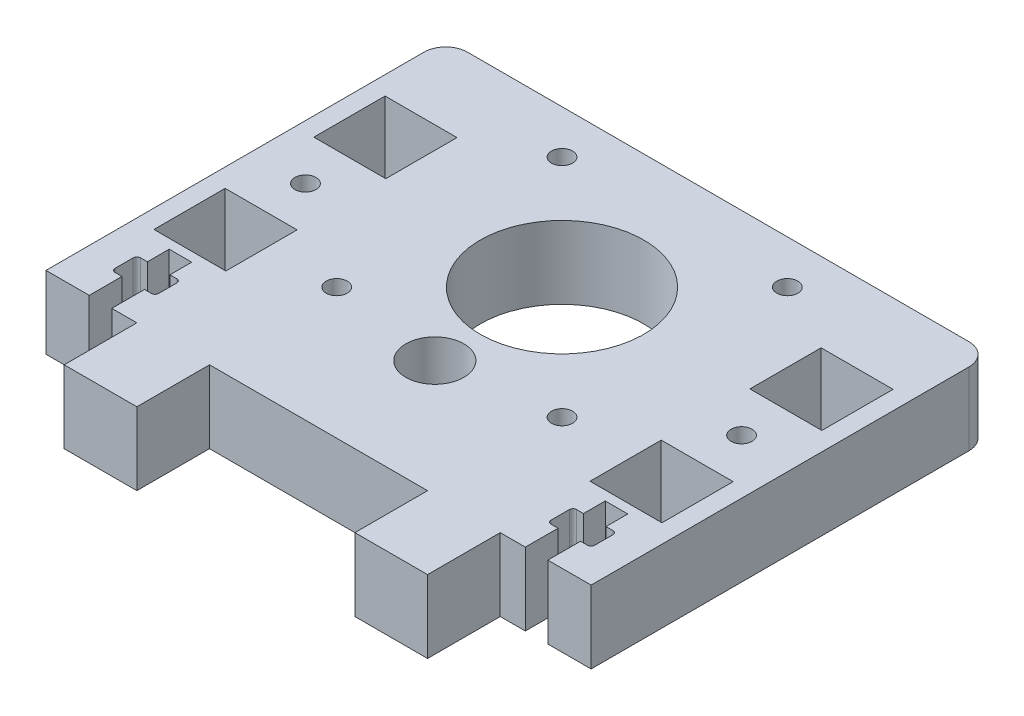
SolidWorks part; units mm, degrees
ref_plane "Front Plane" through (0, 0, 0) normal (0, 0, 1) x (1, 0, 0)
ref_plane "Top Plane" through (0, 0, 0) normal (0, 1, 0) x (1, 0, 0)
ref_plane "Right Plane" through (0, 0, 0) normal (1, 0, 0) x (0, 0, -1)
sketch "Sketch1" plane through (0, 0, 0) normal (0, 1, 0) x (1, 0, 0)
  line L0 (0, 29) -> (0, -6) construction
  line L1 (-34.5, 29) -> (0, 29)
  line L2 (-37.5, 26) -> (-37.5, -26)
  line L3 (-37.5, -26) -> (-25, -26)
  line L4 (0, 29) -> (0, 18.75)
  line L5 (0, -3.75) -> (0, -6)
  line L6 (0, -14) -> (0, -26) construction
  line L7 (-11.25, 7.5) -> (0, 7.5) construction
  line L8 (0, -14) -> (0, -26)
  line L9 (-30, 18.1) -> (-30, 8.3) construction
  line L10 (-37.5, 2.2) -> (0, 2.2) construction
  line L11 (-34.95, 18.1) -> (-25.05, 18.1)
  line L12 (-34.95, 18.1) -> (-34.95, 8.3)
  line L13 (-34.95, 8.3) -> (-25.05, 8.3)
  line L14 (-25.05, 18.1) -> (-25.05, 8.3)
  line L15 (-34.95, 18.1) -> (-25.05, 8.3) construction
  line L16 (-34.95, 8.3) -> (-25.05, 18.1) construction
  line L17 (-34.95, -3.9) -> (-25.05, -13.7) construction
  line L18 (-34.95, -13.7) -> (-25.05, -3.9) construction
  line L19 (-25.05, -13.7) -> (-25.05, -3.9)
  line L20 (-34.95, -3.9) -> (-25.05, -3.9)
  line L21 (-34.95, -13.7) -> (-34.95, -3.9)
  line L22 (-34.95, -13.7) -> (-25.05, -13.7)
  line L23 (-30, -3.9) -> (-30, -13.7) construction
  line L24 (-30, -8.8) -> (-30, 13.2) construction
  line L25 (0, 7.5) -> (-15.5, 23) construction
  line L35 (-15, -26) -> (0, -26)
  line L43 (-20, -36) -> (-20, -24.5) construction
  line L44 (-15, -26) -> (-15, -36)
  line L45 (-15, -36) -> (-25, -36)
  line L46 (-25, -36) -> (-25, -26)
  arc A1 (-34.5, 29) -> (-37.5, 26) centre (-34.5, 26) ccw
  arc A2 (0, 18.75) -> (0, -3.75) centre (0, 7.5) ccw
  circle A4 centre (-15.5, 23) radius 1.45
  circle A6 centre (-15.5, -8) radius 1.45
  circle A7 centre (-30, 2.2) radius 1.45
  arc A10 (0, -6) -> (0, -14) centre (0, -10) ccw
  point P0 (0, 0)
  point P28 (-30, 13.2)
  point P39 (-30, -8.8)
  dimension "D7" = 22.5
  dimension "D17" = 8
  dimension "D14" = 2.9
  dimension "D6" = 3
  dimension "D19" = 2.9
  dimension "D1" = 55
  dimension "D9" = 9.9
  dimension "D10" = 9.8
  dimension "D22" = 10
  dimension "D23" = 10
  dimension "D16" = 17.5
  dimension "D11" = 22
  dimension "D13" = 2.2
  dimension "D3" = 37.5
  dimension "D4" = 31
  dimension "D5" = 15.5
  dimension "D15" = 26
  dimension "D18" = 37.5
  dimension "D20" = 20
  dimension "D8" = 16
  dimension "D12" = 30
extrude "MainLayout" add sketch "Sketch1" along normal blind 10
sketch "Sketch2" plane through (0, 10, 0) normal (0, 1, 0) x (1, 0, 0)
  line L0 (-30, -26) -> (-30, -15) construction
  line L1 (-28.45, -21.5) -> (-28.45, -26)
  line L2 (-37.5, -26) -> (-25, -26) construction
  line L3 (-28.45, -15) -> (-31.55, -15)
  line L4 (-31.55, -15) -> (-31.55, -18)
  line L5 (-31.55, -18) -> (-32.5, -18)
  line L6 (-33, -18.5) -> (-33, -21)
  line L7 (-32.5, -21.5) -> (-31.55, -21.5)
  line L8 (-31.55, -21.5) -> (-31.55, -26)
  line L9 (-31.55, -26) -> (-28.45, -26)
  line L10 (-27.5, -21.5) -> (-28.45, -21.5)
  line L11 (-27, -18.5) -> (-27, -21)
  line L12 (-28.45, -18) -> (-27.5, -18)
  line L13 (-28.45, -15) -> (-28.45, -18)
  line L14 (0, -26) -> (0, -14) construction
  line L30 (-30, -26) -> (-30, -15) construction
  arc A0 (-27, -18.5) -> (-27.5, -18) centre (-27.5, -18.5) ccw
  arc A1 (-32.5, -18) -> (-33, -18.5) centre (-32.5, -18.5) ccw
  arc A2 (-27.5, -21.5) -> (-27, -21) centre (-27.5, -21) ccw
  arc A3 (-33, -21) -> (-32.5, -21.5) centre (-32.5, -21) ccw
  point P17 (0, -20)
  point P38 (-27, -18)
  point P41 (-33, -18)
  point P44 (-27, -21.5)
  point P47 (-33, -21.5)
  dimension "D8" = 0.5
  dimension "D1" = 1.55
  dimension "D2" = 0
  dimension "D3" = 3.5
  dimension "D5" = 11
  dimension "D6" = 3
  dimension "D4" = 8
  dimension "D7" = 30
extrude "TSlot" cut sketch "Sketch2" against normal through all
mirror "Mirror1" about plane through (0, 0, 0) normal (1, 0, 0) of "TSlot", "MainLayout"
equation "\"Y-ROD-SPACING\"=75"
equation "\"Y-BED-OFFSET\"=2"
equation "\"Y-BED-ROD-INSET\"=3.5"
equation "\"T-SLOT-NUT-FILLET-RADIUS\"=0.5"
equation "\"T-SLOT-SCREW-SHAFT-RADIUS\"=1.55"
equation "\"T-SLOT-SCREW-SHAFT-CUTOUT-LENGTH\"=11.0"
equation "\"T-SLOT-NUT-DEPTH\"=3.5"
equation "\"T-SLOT-NUT-WIDTH\"=2.85"
equation "\"T-SLOT-NUT-END-DISTANCE\"=8"
equation "\"ACRYLIC-TAB-CUTOUT-SIZE\"=\"ACRYLIC-THICKNESS\"+\"ACRYLIC-TAB-TOLERANCE\"*2"
equation "\"ACRYLIC-TAB-WIDTH\"=\"ACRYLIC-THICKNESS\""
equation "\"ACRYLIC-M3-HOLE\"=2.9"
equation "\"SMOOTHROD-CAP-SCREW-DISTANCE\"=20"
equation "\"FRAME-WIDTH-INNER\"=370"
equation "\"NEMA17-HOLE-SPACING\"=31"
equation "\"NEMA17-CENTRAL-CUTOUT\"=22.5"
equation "\"D7@Sketch1\"=\"NEMA17-CENTRAL-CUTOUT\""
equation "\"D5@Sketch1\"=\"NEMA17-HOLE-SPACING\"/2"
equation "\"D4@Sketch1\"=\"NEMA17-HOLE-SPACING\""
equation "\"D19@Sketch1\"=\"ACRYLIC-M3-HOLE\""
equation "\"D14@Sketch1\"=\"ACRYLIC-M3-HOLE\""
equation "\"D9@Sketch1\"=\"ACRYLIC-THICKNESS\"-\"KERF\"*2"
equation "\"D10@Sketch1\"=\"ACRYLIC-TAB-WIDTH\"-\"KERF\"*4"
equation "\"D23@Sketch1\"=\"ACRYLIC-TAB-WIDTH\""
equation "\"D22@Sketch1\"=\"ACRYLIC-TAB-WIDTH\""
equation "\"D5@Sketch2\"=\"T-SLOT-SCREW-SHAFT-CUTOUT-LENGTH\""
equation "\"D4@Sketch2\"=\"T-SLOT-NUT-END-DISTANCE\""
equation "\"D3@Sketch2\"=\"T-SLOT-NUT-DEPTH\""
equation "\"D1@Sketch2\"=\"T-SLOT-SCREW-SHAFT-RADIUS\""
equation "\"D8@Sketch2\"=\"T-SLOT-NUT-FILLET-RADIUS\""
equation "\"Z-BRACKET-REACH\"=55"
equation "\"D1@Sketch1\"=\"Z-BRACKET-REACH\""
equation "\"Z-ROD-SPACING\"=17.5"
equation "\"ACRYLIC-THICKNESS\"=10"
equation "\"TOP-BRACKET-SPACING\"=40"
equation "\"SMOOTHROD-X-LENGTH\"=350"
equation "\"SMOOTHROD-Y-LENGTH\"=350"
equation "\"SMOOTHROD-Z-LENGTH\"=350"
equation "\"SMOOTHROD-TIGHTENING-HEADROOM\"=.25"
equation "\"LEADSCREW-Z-LENGTH\"=300"
equation "\"D16@Sketch1\"=\"Z-ROD-SPACING\""
equation "\"X-ROD-SPACING\"=45"
equation "\"ACRYLIC-THICKNESS2\"=4.5"
equation "\"SCREW-LENGTH-FRAME\"=\"ACRYLIC-THICKNESS\" + 10"
equation "\"SCREW-HEAD-RADIUS\"=6"
equation "\"PRINTED-X-SMOOTHROD-DIAMETER\"=8.4"
equation "\"PRINTED-X-SMOOTHROD-CUTOUT\"=10"
equation "\"PRINTED-X-BASE-HEIGHT\"=10"
equation "\"PRINTED-LM8UU-CUTOUT-SIZE\"=15.5"
equation "\"PRINTED-LM8UU-CUTOUT-LENGTH\"=24.5"
equation "\"PRINTED-X-IDLER-HEIGHT\"=16"
equation "\"PSU-MOUNTING-WIDTH\"=95"
equation "\"PSU-MOUNTING-HEIGHT\"=177"
equation "\"D1@MainLayout\"=\"ACRYLIC-THICKNESS\""
equation "\"Z-ROD-INSET\"=16"
equation "\"Y-BELT-TO-ROD-DISTANCE\"=20"
equation "\"SPOOL-HOLDER-ROD-SPACING\"=150"
equation "\"D8@Sketch1\"=\"Z-ROD-INSET\""
equation "\"Y-BED-SCREW-SPACING\"=209"
equation "\"Y-BED-SCREW-CUTOUT-SLOT-HEIGHT\"=2"
equation "\"ACRYLIC-TAB-TOLERANCE\"=-.05"
equation "\"SCREW-LENGTH-MOTOR\"=\"ACRYLIC-THICKNESS\" + 5"
equation "\"SCREW-LENGTH-EXTRUDER\"=28"
equation "\"ACRYLIC-X-CARRIAGE-WIDTH\"=55"
equation "\"ACRYLIC-X-CARRIAGE-HEIGHT\"=75"
equation "\"ACRYLIC-X-CARRIAGE-LM8UU-CUTOUT-WIDTH\"=24.25"
equation "\"ACRYLIC-X-CARRIAGE-SCREW-SPACING-X\"=15"
equation "\"ACRYLIC-X-CARRIAGE-SCREW-SPACING-Y\"=33"
equation "\"ACRYLIC-X-CARRIAGE-CENTER-TAB-SPACING\"=14"
equation "\"ACRYLIC-X-CARRIAGE-EXTRUDER-OFFSET\"=26"
equation "\"ACRYLIC-X-CARRIAGE-EXTRUDER-ANGLE\"=90"
equation "\"ACRYLIC-X-CARRIAGE-EXTRUDER-SHELF-DEPTH\"=\"ACRYLIC-X-CARRIAGE-EXTRUDER-OFFSET\" + 28"
equation "\"ACRYLIC-X-CARRIAGE-EXTRUDER-BRACE-SPACING\"=23"
equation "\"ACRYLIC-X-CARRIAGE-EXTRUDER-BRACE-TAB-OFFSET\"=20"
equation "\"ACRYLIC-X-CARRIAGE-EXTRUDER-BRACE-HEIGHT\"=35"
equation "\"ACRYLIC-X-CARRIAGE-EXTRUDER-BRACE-SCREW-SPACING\"=22"
equation "\"KERF\"=0.05"
equation "\"PRINTED-M3-HOLE\"=3.5"
equation "\"PRINTED-M3-NUT-AF\"=6.25"
equation "\"ACRYLIC-X-CARRIAGE-LM8UU-CUTOUT-HEIGHT\"=11.0"
equation "\"ACRYLIC-X-CARRIAGE-DUAL-WIDTH-MULTIPLIER\"=1.65"
equation "\"ACRYLIC-X-CARRIAGE-DUAL-HOTEND-SPACING\"=42"
equation "\"ACRYLIC-X-CARRIAGE-DUAL-WIDTH\"=75"
equation "\"ACRYLIC-X-CARRIAGE-DUAL-FAN-OFFSET\"=52"
equation "\"ACRYLIC-X-CARRIAGE-DUAL-FAN-HEIGHT\"=20"
equation "\"ACRYLIC-X-CARRIAGE-DUAL-HOTEND-SEPARATION\"=36"
equation "\"ACRYLIC-X-CARRIAGE-DUAL-MOUNT-PLATE-DEPTH\"=75"
equation "\"ACRYLIC-X-CARRIAGE-DUAL-MOUNT-BRACE-WIDTH\"=33"
equation "\"ACRYLIC-X-CARRIAGE-DUAL-MOUNT-SCREW-WIDTH\"=40"
equation "\"BLOWER-FAN-WIDTH\"=15"
